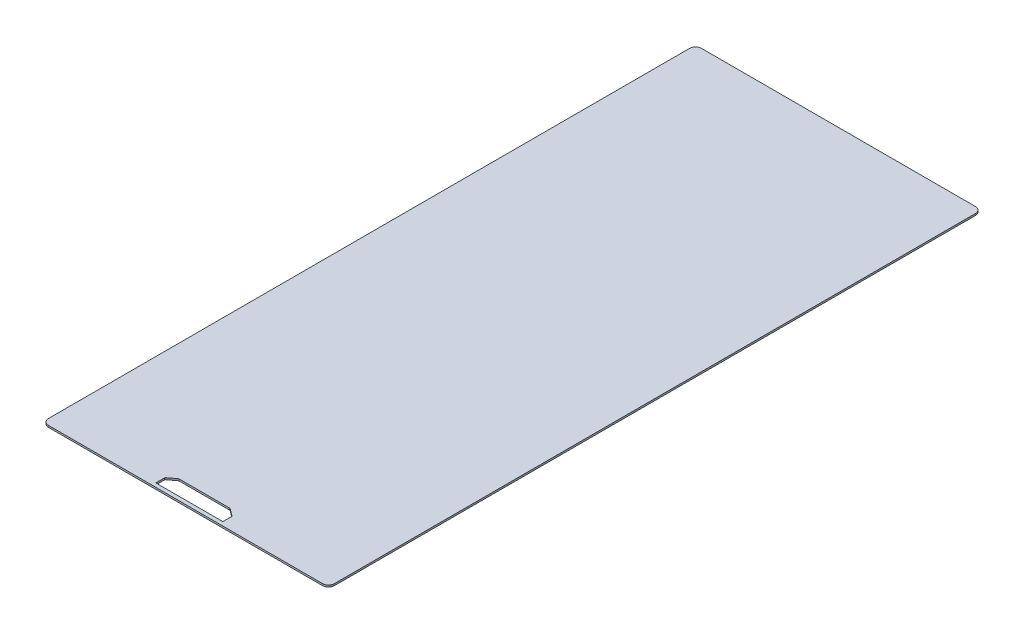
SolidWorks part; units mm, degrees
ref_plane "Front Plane" through (0, 0, 0) normal (0, 0, 1) x (1, 0, 0)
ref_plane "Top Plane" through (0, 0, 0) normal (0, 1, 0) x (1, 0, 0)
ref_plane "Right Plane" through (0, 0, 0) normal (1, 0, 0) x (0, 0, -1)
sketch "Sketch1" plane through (0, 0, 0) normal (0, 1, 0) x (1, 0, 0)
  line L1 (-231.5, -551.5) -> (231.5, -551.5)
  line L2 (-241.5, -541.5) -> (-241.5, 541.5)
  line L3 (-231.5, 551.5) -> (231.5, 551.5)
  line L4 (241.5, -541.5) -> (241.5, 541.5)
  line L5 (-241.5, -551.5) -> (241.5, 551.5) construction
  line L6 (-241.5, 551.5) -> (241.5, -551.5) construction
  arc A0 (231.5, -551.5) -> (241.5, -541.5) centre (231.5, -541.5) ccw
  arc A1 (-231.5, -551.5) -> (-241.5, -541.5) centre (-231.5, -541.5) cw
  arc A2 (-241.5, 541.5) -> (-231.5, 551.5) centre (-231.5, 541.5) cw
  arc A3 (231.5, 551.5) -> (241.5, 541.5) centre (231.5, 541.5) cw
  point P0 (0, 0)
  dimension "D3" = 10
  dimension "D1" = 483
  dimension "D2" = 1103
extrude "Boss-Extrude1" add sketch "Sketch1" along normal blind 3
sketch "Sketch2" plane through (0, 3, 0) normal (0, 1, 0) x (1, 0, 0)
  line L0 (0, -551.5) -> (0, -545) construction
  line L1 (-231.5, -551.5) -> (231.5, -551.5) construction
  line L2 (-56.625, -545) -> (56.625, -545)
  line L3 (56.625, -545) -> (56.625, -530.7495)
  line L4 (55.6257, -528.75) -> (43.9683, -520.0005)
  line L5 (42.4676, -519.5) -> (-42.4676, -519.5)
  line L6 (-43.9683, -520.0005) -> (-55.6257, -528.75)
  line L7 (-56.625, -530.7495) -> (-56.625, -545)
  arc A0 (56.625, -530.7495) -> (55.6257, -528.75) centre (54.125, -530.7495) ccw
  arc A1 (43.9683, -520.0005) -> (42.4676, -519.5) centre (42.4676, -522) ccw
  arc A2 (-55.6257, -528.75) -> (-56.625, -530.7495) centre (-54.125, -530.7495) ccw
  arc A3 (-42.4676, -519.5) -> (-43.9683, -520.0005) centre (-42.4676, -522) ccw
  point P8 (0, -545)
  point P15 (56.625, -529.5)
  point P18 (43.3014, -519.5)
  point P23 (-43.3014, -519.5)
  dimension "D6" = 2.5
  dimension "D1" = 113.25
  dimension "D2" = 15.5
  dimension "D3" = 25.5
  dimension "D4" = 86.6028
  dimension "D5" = 6.5
extrude "Cut-Extrude1" cut sketch "Sketch2" against normal through all
